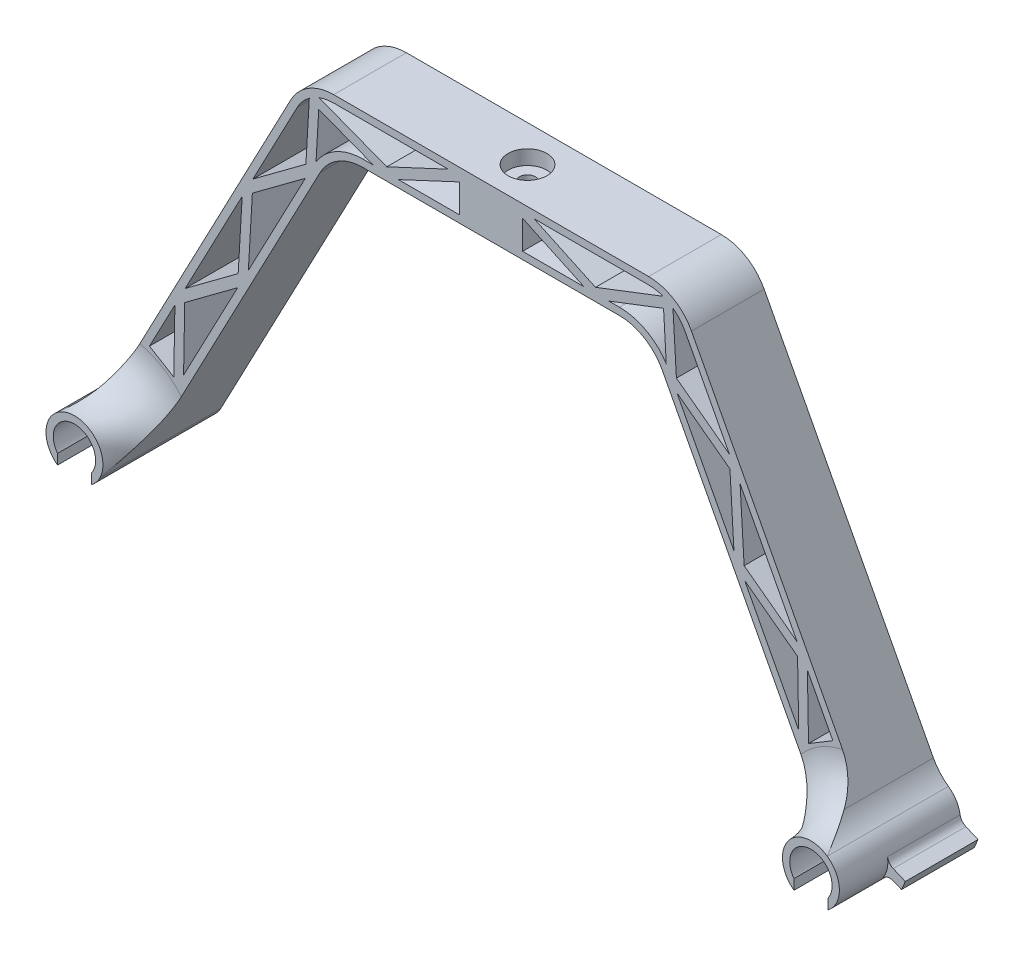
SolidWorks part; units mm, degrees
ref_plane "Front Plane" through (0, 0, 0) normal (0, 0, 1) x (1, 0, 0)
ref_plane "Top Plane" through (0, 0, 0) normal (0, 1, 0) x (1, 0, 0)
ref_plane "Right Plane" through (0, 0, 0) normal (1, 0, 0) x (0, 0, -1)
sketch "Sketch1" plane through (0, 0, 0) normal (0, 0, 1) x (1, 0, 0)
  line L0 (-49.8045, 21.327) -> (15.1955, 21.327)
  line L1 (-55.8405, 31.327) -> (21.2314, 31.327)
  line L2 (-17.3045, 21.327) -> (-17.3045, 31.327) construction
  line L3 (15.1955, 21.327) -> (53.4971, -51.4103)
  line L4 (21.2314, 31.327) -> (58.9694, -40.3399)
  line L5 (24.0437, 25.9863) -> (62.3454, -46.751) construction
  line L6 (58.6955, -48.673) -> (58.6955, -58.8319) construction
  line L7 (55.1955, -51.298) -> (55.1955, -53.3916)
  line L8 (62.1955, -51.298) -> (62.1955, -53.3916)
  line L9 (65.8247, -51.4951) -> (67.3953, -52.1632)
  line L10 (55.1955, -48.673) -> (55.1955, -58.8319) construction
  line L11 (62.1955, -48.673) -> (62.1955, -58.8319) construction
  line L12 (67.3953, -52.1632) -> (68.1781, -50.3228)
  line L13 (68.1781, -50.3228) -> (65.6878, -49.2634)
  line L14 (-93.3045, -48.673) -> (-93.3045, -58.8319) construction
  line L15 (-102.7872, -50.3228) -> (-100.2968, -49.2634)
  line L16 (-102.0043, -52.1632) -> (-102.7872, -50.3228)
  line L17 (-100.4338, -51.4951) -> (-102.0043, -52.1632)
  line L18 (-96.8045, -51.298) -> (-96.8045, -53.3916)
  line L19 (-89.8045, -51.298) -> (-89.8045, -53.3916)
  line L20 (-55.8405, 31.327) -> (-93.5785, -40.3399)
  line L21 (-49.8045, 21.327) -> (-88.1062, -51.4103)
  arc A0 (62.1955, -51.298) -> (55.1955, -51.298) centre (58.6955, -48.673) ccw
  arc A1 (53.4971, -51.4103) -> (55.1955, -53.3916) centre (58.6955, -48.673) ccw
  arc A2 (62.1955, -53.3916) -> (63.4301, -52.1514) centre (58.6955, -48.673) ccw
  arc A3 (58.9694, -40.3399) -> (62.0714, -43.8648) centre (67.8176, -35.6806) ccw
  arc A4 (64.496, -47.7405) -> (62.0714, -43.8648) centre (58.6955, -48.673) ccw
  arc A5 (63.4301, -52.1514) -> (65.8247, -51.4951) centre (65.0418, -53.3355) cw
  arc A6 (64.496, -47.7405) -> (65.6878, -49.2634) centre (66.4706, -47.423) ccw
  arc A7 (-99.1051, -47.7405) -> (-100.2968, -49.2634) centre (-101.0797, -47.423) cw
  arc A8 (-98.0391, -52.1514) -> (-100.4338, -51.4951) centre (-99.6509, -53.3355) ccw
  arc A9 (-99.1051, -47.7405) -> (-96.6805, -43.8648) centre (-93.3045, -48.673) cw
  arc A10 (-93.5785, -40.3399) -> (-96.6805, -43.8648) centre (-102.4267, -35.6806) cw
  arc A11 (-96.8045, -53.3916) -> (-98.0391, -52.1514) centre (-93.3045, -48.673) cw
  arc A12 (-88.1062, -51.4103) -> (-89.8045, -53.3916) centre (-93.3045, -48.673) cw
  arc A13 (-96.8045, -51.298) -> (-89.8045, -51.298) centre (-93.3045, -48.673) cw
  point P0 (-99.1784, -48.7877)
  point P28 (64.1746, -50.7932)
  point P31 (64.5693, -48.7877)
  point P44 (-98.7836, -50.7932)
  dimension "D2" = 8.75
  dimension "D3" = 11.75
  dimension "D9" = 10
  dimension "D12" = 2
  dimension "D1" = 65
  dimension "D4" = 70
  dimension "D5" = 76
  dimension "D10" = 2
  dimension "D11" = 3.5
  dimension "D13" = 10
  dimension "D6" = 10
  dimension "D7" = 3.5
  dimension "D8" = 3.5
extrude "Boss-Extrude1" add sketch "Sketch1" along normal blind 15
sketch "Sketch2" plane through (0, 0, 15) normal (0, 0, 1) x (1, 0, 0)
  line L0 (55.1955, -51.298) -> (55.1955, -53.3916)
  line L1 (55.1955, -53.3916) -> (55.1955, -51.298) construction
  line L2 (62.1955, -51.298) -> (62.1955, -53.3916)
  line L3 (62.1955, -51.298) -> (62.1955, -53.3916) construction
  line L4 (-17.3045, 31.327) -> (-17.3045, 21.327) construction
  line L5 (21.2314, 31.327) -> (-55.8405, 31.327) construction
  line L6 (-49.8045, 21.327) -> (15.1955, 21.327) construction
  line L7 (-96.8045, -51.298) -> (-96.8045, -53.3916)
  line L8 (-89.8045, -51.298) -> (-89.8045, -53.3916)
  arc A0 (62.1955, -51.298) -> (55.1955, -51.298) centre (58.6955, -48.673) ccw
  arc A1 (62.1955, -53.3916) -> (55.1955, -53.3916) centre (58.6955, -48.673) ccw
  arc A2 (-96.8045, -51.298) -> (-89.8045, -51.298) centre (-93.3045, -48.673) cw
  arc A3 (-96.8045, -53.3916) -> (-89.8045, -53.3916) centre (-93.3045, -48.673) cw
extrude "Boss-Extrude2" add sketch "Sketch2" along normal blind 10
fillet "Fillet1" radius 10 2 edges at (54.8142, -44.2626, 15) (-89.4233, -44.2626, 15)
fillet "Fillet2" radius 10 4 edges at (21.2314, 31.327, 7.5) (-55.8405, 31.327, 7.5) (15.1955, 21.327, 7.5) (-49.8045, 21.327, 7.5)
sketch "Sketch3" plane through (0, 21.327, 0) normal (0, -1, 0) x (-1, 0, 0)
  line L0 (17.3045, -15) -> (17.3045, 0) construction
  line L1 (43.7686, -15) -> (-9.1595, -15) construction
  line L2 (43.7686, 0) -> (-9.1595, 0) construction
  circle A0 centre (17.3045, -7.5) radius 1.65
  dimension "D1" = 3.3
extrude "Cut-Extrude1" cut sketch "Sketch3" against normal blind 10
sketch "Sketch5" plane through (0, 0, 15) normal (0, 0, 1) x (1, 0, 0)
  line L0 (-52.6168, 15.9863) -> (-81.2348, -38.361)
  line L1 (-43.7686, 21.327) -> (-22.3045, 21.327)
  line L2 (-43.7686, 21.327) -> (9.1595, 21.327) construction
  line L3 (-22.3045, 21.327) -> (-22.3045, 31.327)
  line L4 (15.1955, 31.327) -> (-49.8045, 31.327) construction
  line L5 (-22.3045, 31.327) -> (-49.8045, 31.327)
  line L6 (-58.6528, 25.9863) -> (-89.8119, -33.1869)
  line L7 (-89.8119, -33.1869) -> (-81.2348, -38.361)
  line L8 (-17.3045, 31.327) -> (-17.3045, 21.327) construction
  line L9 (-12.3045, 21.327) -> (-12.3045, 31.327)
  line L10 (-82.8393, -19.906) -> (-74.2621, -25.0801)
  line L11 (32.3549, 5.0483) -> (18.9876, 14.9763)
  line L12 (-75.8667, -6.6251) -> (-67.2895, -11.7992)
  line L13 (22.7165, 25.2874) -> (53.2162, -32.6336)
  line L14 (-68.894, 6.6558) -> (-60.3169, 1.4817)
  line L15 (19.335, 16.6852) -> (47.2122, -36.2554)
  line L16 (-61.9214, 19.9367) -> (-53.3442, 14.7626)
  line L17 (34.285, 6.6558) -> (25.7078, 1.4817)
  line L18 (-54.9488, 33.2176) -> (-46.3716, 28.0435)
  line L19 (-53.9441, 16.6852) -> (-81.8213, -36.2554)
  line L20 (-87.8253, -32.6336) -> (-81.8213, -36.2554)
  line L21 (-57.3255, 25.2874) -> (-87.8253, -32.6336)
  line L22 (-23.8045, 29.827) -> (-49.8045, 29.827)
  line L23 (-23.8045, 22.827) -> (-23.8045, 29.827)
  line L24 (-43.7686, 22.827) -> (-23.8045, 22.827)
  line L25 (-38.8045, 22.827) -> (-38.8045, 29.827)
  line L26 (-53.8045, 22.827) -> (-53.8045, 29.827)
  line L27 (-81.8213, -36.2554) -> (-81.537, -20.6917) construction
  line L28 (-81.537, -20.6917) -> (-68.5446, -11.0421) construction
  line L29 (-68.5446, -11.0421) -> (-67.5602, 5.8511) construction
  line L30 (-67.5602, 5.8511) -> (-54.5678, 15.5007) construction
  line L31 (-54.5678, 15.5007) -> (-53.8045, 28.5991) construction
  line L32 (-53.8045, 28.5991) -> (-38.8045, 22.827) construction
  line L33 (-38.8045, 22.827) -> (-23.8045, 29.827) construction
  line L34 (-80.8214, -36.2737) -> (-80.5461, -21.2014)
  line L35 (-80.5461, -21.2014) -> (-67.5734, -11.5665)
  line L36 (-67.5734, -11.5665) -> (-66.5619, 5.793)
  line L37 (-82.8211, -36.2372) -> (-82.5278, -20.1819)
  line L38 (-82.5278, -20.1819) -> (-69.5157, -10.5177)
  line L39 (-69.5157, -10.5177) -> (-68.5585, 5.9093)
  line L40 (-66.9639, 5.0483) -> (-53.5966, 14.9763)
  line L41 (-53.5966, 14.9763) -> (-52.8859, 27.1741)
  line L42 (-52.8859, 27.1741) -> (-38.7669, 21.7411)
  line L43 (-38.7669, 21.7411) -> (-23.3816, 28.9208)
  line L44 (-68.1564, 6.6539) -> (-55.5389, 16.0251)
  line L45 (-55.5389, 16.0251) -> (-54.7232, 30.0241)
  line L46 (-54.7232, 30.0241) -> (-38.8422, 23.913)
  line L47 (-38.8422, 23.913) -> (-24.2274, 30.7332)
  line L48 (-15.3319, 34.6079) -> (-15.3319, 44.6079) [skipped]
  line L49 (-8.3593, 47.8888) -> (-8.3593, 57.8888) [skipped]
  line L50 (-1.3866, 61.1697) -> (-1.3866, 71.1697) [skipped]
  line L51 (5.586, 74.4506) -> (5.586, 84.4506) [skipped]
  line L52 (12.5586, 87.7315) -> (12.5586, 97.7315) [skipped]
  line L53 (24.0437, 25.9863) -> (55.2029, -33.1869)
  line L54 (-12.3045, 31.327) -> (15.1955, 31.327)
  line L55 (18.0078, 15.9863) -> (46.6257, -38.361)
  line L56 (4.1955, 22.827) -> (-10.8045, 29.827) construction
  line L57 (19.1955, 28.5991) -> (4.1955, 22.827) construction
  line L58 (19.9587, 15.5007) -> (19.1955, 28.5991) construction
  line L59 (32.9511, 5.8511) -> (19.9587, 15.5007) construction
  line L60 (20.1141, 30.0241) -> (4.2331, 23.913)
  line L61 (20.9299, 16.0251) -> (20.1141, 30.0241)
  line L62 (33.5474, 6.6539) -> (20.9299, 16.0251)
  line L63 (4.1578, 21.7411) -> (-11.2274, 28.9208)
  line L64 (18.2768, 27.1741) -> (4.1578, 21.7411)
  line L65 (18.9876, 14.9763) -> (18.2768, 27.1741)
  line L66 (19.1955, 22.827) -> (19.1955, 29.827)
  line L67 (4.1955, 22.827) -> (4.1955, 29.827)
  line L68 (9.1595, 22.827) -> (-10.8045, 22.827)
  line L69 (-10.8045, 22.827) -> (-10.8045, 29.827)
  line L70 (20.3397, 33.2176) -> (11.7626, 28.0435)
  line L71 (27.3123, 19.9367) -> (18.7352, 14.7626)
  line L72 (9.1595, 21.327) -> (-12.3045, 21.327)
  line L73 (33.9355, -11.0421) -> (32.9511, 5.8511) construction
  line L74 (46.9279, -20.6917) -> (33.9355, -11.0421) construction
  line L75 (47.2122, -36.2554) -> (46.9279, -20.6917) construction
  line L76 (34.9066, -10.5177) -> (33.9494, 5.9093)
  line L77 (47.9187, -20.1819) -> (34.9066, -10.5177)
  line L78 (48.212, -36.2372) -> (47.9187, -20.1819)
  line L79 (32.9644, -11.5665) -> (31.9528, 5.793)
  line L80 (45.937, -21.2014) -> (32.9644, -11.5665)
  line L81 (46.2124, -36.2737) -> (45.937, -21.2014)
  line L82 (53.2162, -32.6336) -> (47.2122, -36.2554)
  line L83 (41.2576, -6.6251) -> (32.6804, -11.7992)
  line L84 (48.2302, -19.906) -> (39.6531, -25.0801)
  line L85 (55.2029, -33.1869) -> (46.6257, -38.361)
  line L86 (-10.8045, 29.827) -> (15.1955, 29.827)
  line L87 (4.2331, 23.913) -> (-10.3816, 30.7332)
  arc A0 (-58.6528, 25.9863) -> (-49.8045, 31.327) centre (-49.8045, 21.327) cw
  arc A1 (-52.6168, 15.9863) -> (-43.7686, 21.327) centre (-43.7686, 11.327) cw
  arc A2 (-57.3255, 25.2874) -> (-49.8045, 29.827) centre (-49.8045, 21.327) cw
  arc A3 (-53.9441, 16.6852) -> (-43.7686, 22.827) centre (-43.7686, 11.327) cw
  arc A4 (19.335, 16.6852) -> (9.1595, 22.827) centre (9.1595, 11.327) ccw
  arc A5 (22.7165, 25.2874) -> (15.1955, 29.827) centre (15.1955, 21.327) ccw
  arc A6 (18.0078, 15.9863) -> (9.1595, 21.327) centre (9.1595, 11.327) ccw
  arc A7 (24.0437, 25.9863) -> (15.1955, 31.327) centre (15.1955, 21.327) ccw
  dimension "D1" = 5
  dimension "D3" = 1.5
  dimension "D5" = 1
  dimension "D6" = 1
  dimension "D7" = 1
  dimension "D8" = 1
  dimension "D2" = 6
  dimension "D4" = 3
extrude "Cut-Extrude2" cut sketch "Sketch5" along direction (0, 0, 1) on the side against the normal offset from surface (12.5 mm away) 2.5 contours L20 L37 L21 | L34 L19 L10 | L35 L34 L10 L19 | L38 L39 L12 L21 | L12 L39 L21 | L36 L19 L14 | L40 L36 L14 L19 | L44 L45 L16 L21 | A2 L21 L16 L45 | L41 A3 L24 L42 | A2 L46 L47 L25 L22 | L25 L47 L22 | L43 L24 L23 | L69 L68 L63 | L87 L67 L86 | L60 A5 L86 L67 L87 | A4 L65 L64 L68 | L13 A5 L61 L71 | L13 L71 L61 L62 | L17 L79 L11 L15 | L15 L79 L17 | L83 L13 L76 | L13 L83 L76 L77 | L84 L81 L80 L15 | L81 L84 L15 | L82 L13 L78 region at (-70.9158, -4.7222, 15) region at (-74.8263, -12.1834, 15) region at (-75.255, -19.5503, 15) region at (-78.9553, -26.6299, 15) region at (-84.403, -30.3172, 15) region at (-43.7628, 27.8138, 15) region at (-57.0169, 21.481, 15) region at (-60.8495, 14.3594, 15) region at (-34.5928, 27.8615, 15) region at (-61.2784, 6.9924, 15) region at (-65.189, -0.4688, 15) region at (-28.0163, 24.7925, 15) region at (-49.866, 23.2132, 15) region at (9.1537, 27.8138, 15) region at (-0.0163, 27.8615, 15) region at (22.4079, 21.481, 15) region at (26.2405, 14.3594, 15) region at (36.3067, -4.7222, 15) region at (40.2172, -12.1834, 15) region at (15.257, 23.2132, 15) region at (-6.5928, 24.7925, 15) region at (49.7939, -30.3172, 15) region at (40.6459, -19.5503, 15) region at (44.3462, -26.6299, 15) region at (26.6694, 6.9924, 15) region at (30.5799, -0.4688, 15) up to face at (-17.3045, -31.9917, 0)
sketch "Sketch6" plane through (0, 31.327, 0) normal (0, 1, 0) x (1, 0, 0)
  circle A0 centre (-17.3045, -7.5) radius 4
  dimension "D1" = 8
extrude "Cut-Extrude3" cut sketch "Sketch6" against normal blind 3
equation "\"D3@Sketch1\"=\"D2@Sketch1\"+3"
